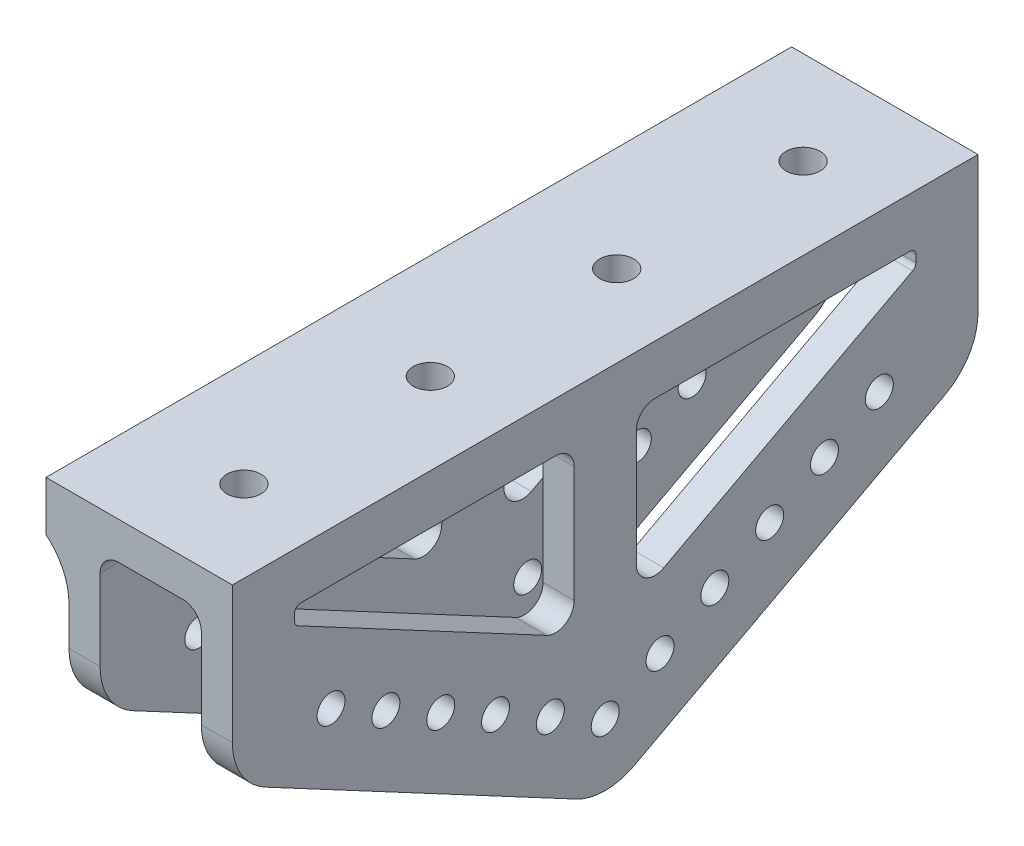
SolidWorks part; units mm, degrees
ref_plane "前视基准面" through (0, 0, 0) normal (0, 0, 1) x (1, 0, 0)
ref_plane "上视基准面" through (0, 0, 0) normal (0, 1, 0) x (1, 0, 0)
ref_plane "右视基准面" through (0, 0, 0) normal (1, 0, 0) x (0, 0, -1)
sketch "Sketch1" plane through (0, 0, 0) normal (1, 0, 0) x (0, 0, -1)
  line L0 (-60, 0) -> (60, 0)
  line L1 (60, 0) -> (60, -28)
  line L2 (60, -28) -> (0, -60)
  line L3 (0, -60) -> (-60, -28)
  line L4 (-60, -28) -> (-60, 0)
  line L5 (0, 15) -> (0, -37.9294) construction
  line L6 (-60, -16.6667) -> (0, -48.6667) construction
  line L7 (50, -9) -> (50, -10.0667)
  line L8 (49.4706, -10.949) -> (9.4118, -32.3137)
  line L9 (-9.4118, -32.3137) -> (-49.4706, -10.949)
  line L10 (-50, -10.0667) -> (-50, -9)
  line L11 (-49, -8) -> (-8, -8)
  line L12 (-5, -11) -> (-5, -29.6667)
  line L13 (5, -11) -> (5, -29.6667)
  line L14 (8, -8) -> (49, -8)
  circle A0 centre (-44.1176, -25.1373) radius 2.25
  circle A1 centre (-35.2941, -29.8431) radius 2.25
  circle A2 centre (-26.4706, -34.549) radius 2.25
  circle A3 centre (-17.6471, -39.2549) radius 2.25
  circle A4 centre (-8.8235, -43.9608) radius 2.25
  circle A5 centre (0, -48.6667) radius 2.25
  circle A6 centre (0, -48.6667) radius 2.25 construction
  circle A7 centre (8.8235, -43.9608) radius 2.25
  circle A8 centre (17.6471, -39.2549) radius 2.25
  circle A9 centre (26.4706, -34.549) radius 2.25
  circle A10 centre (35.2941, -29.8431) radius 2.25
  circle A11 centre (44.1176, -25.1373) radius 2.25
  arc A12 (-49.4706, -10.949) -> (-50, -10.0667) centre (-49, -10.0667) cw
  arc A13 (50, -10.0667) -> (49.4706, -10.949) centre (49, -10.0667) cw
  arc A14 (50, -9) -> (49, -8) centre (49, -9) ccw
  arc A15 (-50, -9) -> (-49, -8) centre (-49, -9) cw
  arc A16 (5, -11) -> (8, -8) centre (8, -11) cw
  arc A17 (-5, -11) -> (-8, -8) centre (-8, -11) ccw
  arc A18 (5, -29.6667) -> (9.4118, -32.3137) centre (8, -29.6667) ccw
  arc A19 (-5, -29.6667) -> (-9.4118, -32.3137) centre (-8, -29.6667) cw
  point P52 (5, -8)
  point P59 (0, 0)
  point P60 (6.3616, -45.2738)
  point P61 (0, 0)
  point P62 (5.2634, -45.8595)
  point P63 (0, 0)
  point P64 (0, 0)
  dimension "D5" = 4.5
  dimension "D16" = 1
  dimension "D17" = 3
  dimension "D18" = 3
  dimension "D1" = 28
  dimension "D2" = 60
  dimension "D3" = 120
  dimension "D4" = 10
  dimension "D6" = 10
  dimension "D7" = 10
  dimension "D8" = 10
  dimension "D9" = 10
  dimension "D10" = 10
  dimension "D11" = 10
  dimension "D12" = 8
  dimension "D13" = 10
  dimension "D14" = 10
  dimension "D15" = 10
extrude "Boss-Extrude1" add sketch "Sketch1" along normal mid plane 26.3
sketch "Sketch2" plane through (0, 0, -60) normal (0, 0, -1) x (-1, 0, 0)
  line L0 (-13.15, -28) -> (-13.15, 0) construction
  line L1 (-8.15, -6) -> (8.15, -6)
  line L2 (-8.15, -6) -> (-8.15, -60)
  line L3 (-8.15, -60) -> (8.15, -60)
  line L4 (8.15, -6) -> (8.15, -60)
  line L5 (-13.15, 0) -> (13.15, 0) construction
  line L6 (-13.15, -60) -> (13.15, -60) construction
  dimension "D1" = 5
  dimension "D2" = 5
  dimension "D3" = 6
extrude "Cut-Extrude1" cut sketch "Sketch2" against normal through all both and the other way through all
sketch "Sketch3" plane through (0, 0, 0) normal (0, 1, 0) x (1, 0, 0)
  line L0 (0, 60) -> (0, -60) construction
  line L1 (13.15, 60) -> (-13.15, 60) construction
  line L2 (13.15, -60) -> (-13.15, -60) construction
  line L3 (-13.15, 0) -> (13.15, 0) construction
  line L4 (13.15, 60) -> (13.15, -60) construction
  circle A0 centre (0, 45) radius 2.75
  circle A1 centre (0, 15) radius 2.75
  circle A2 centre (0, -15) radius 2.75
  circle A3 centre (0, -45) radius 2.75
  dimension "D1" = 5.5
  dimension "D2" = 30
  dimension "D3" = 30
extrude "Cut-Extrude2" cut sketch "Sketch3" against normal through all
fillet "Fillet1" radius 10 6 edges at (10.65, -28, -60) (-10.65, -28, -60) (-10.65, -28, 60) (10.65, -28, 60) (-10.65, -60, 0) (10.65, -60, 0)
fillet "Fillet2" radius 3 2 edges at (8.15, -6, 0) (-8.15, -6, 0)
sketch "Sketch4" plane through (0, 0, 0) normal (0, 1, 0) x (1, 0, 0)
  line L0 (13.15, -60) -> (-13.15, -60) construction
  line L1 (-13.15, 60) -> (-16.85, 60)
  line L2 (-13.15, 60) -> (-13.15, -60)
  line L3 (-13.15, -60) -> (-16.85, -60)
  line L4 (-16.85, 60) -> (-16.85, -60)
  dimension "D1" = 3.7
extrude "Boss-Extrude2" add sketch "Sketch4" against normal blind 8
fillet "Fillet3" radius 10 3 edges at (-13.15, -8, 54.5) (-13.15, -8, 0) (-13.15, -8, -54.5)
